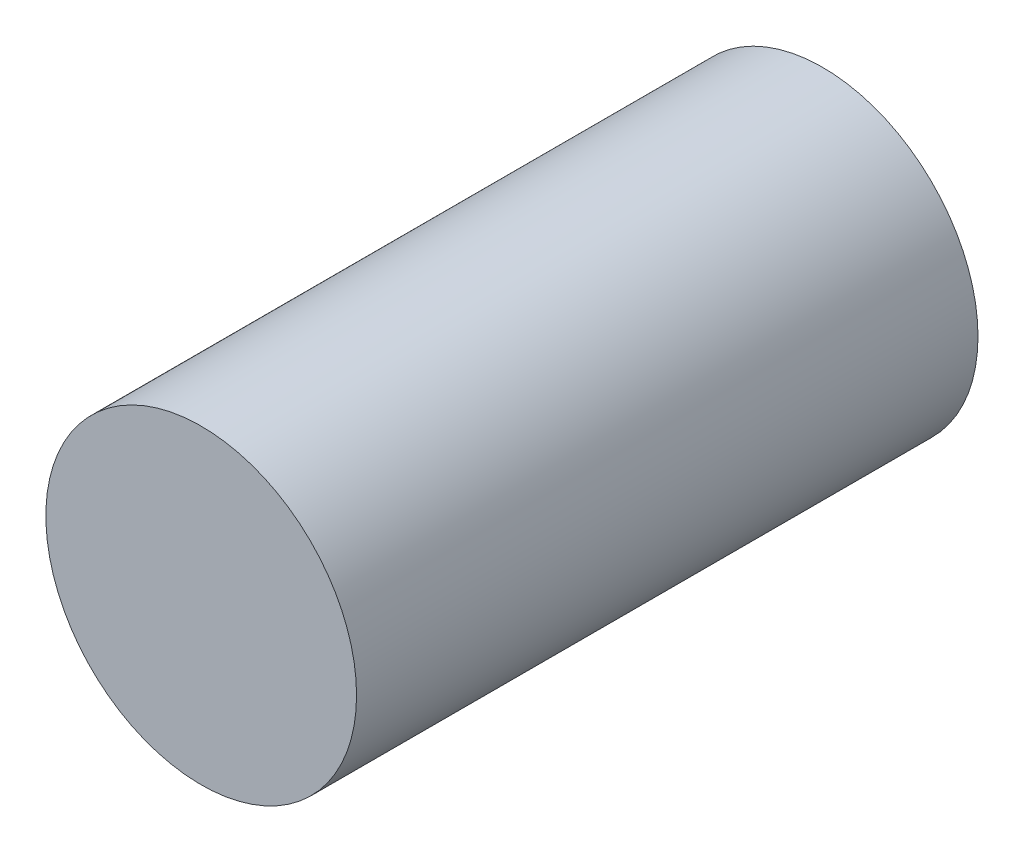
SolidWorks part; units mm, degrees
ref_plane "Front Plane" through (0, 0, 0) normal (0, 0, 1) x (1, 0, 0)
ref_plane "Top Plane" through (0, 0, 0) normal (0, 1, 0) x (1, 0, 0)
ref_plane "Right Plane" through (0, 0, 0) normal (1, 0, 0) x (0, 0, -1)
sketch "Sketch1" plane through (0, 0, 0) normal (0, 0, 1) x (1, 0, 0)
  circle A0 centre (0, 0) radius 6.35
  dimension "D1" = 12.7
extrude "Boss-Extrude1" add sketch "Sketch1" along normal blind 12.7 and the other way blind 12.7
